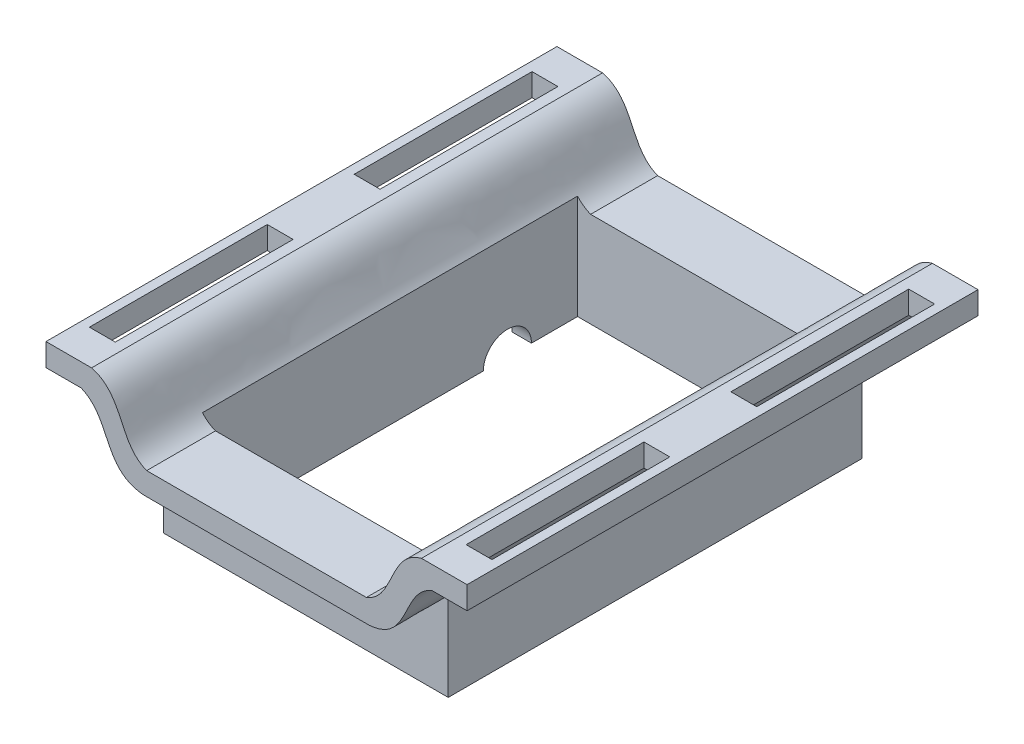
SolidWorks part; units mm, degrees
ref_plane "Front Plane" through (0, 0, 0) normal (0, 0, 1) x (1, 0, 0)
ref_plane "Top Plane" through (0, 0, 0) normal (0, 1, 0) x (1, 0, 0)
ref_plane "Right Plane" through (0, 0, 0) normal (1, 0, 0) x (0, 0, -1)
sketch "Sketch1" plane through (0, 0, 0) normal (0, 0, 1) x (1, 0, 0)
  line L0 (-25.5, 0) -> (25.5, 0) construction
  line L1 (-16.9862, -15) -> (16.9862, -15)
  line L2 (-17.4523, -18.5) -> (17.4523, -18.5)
  line L3 (-25.5, -15) -> (25.5, -15) construction
  line L4 (-25.5, -5.5) -> (-32.5504, -5.5)
  line L5 (-32.5504, -5.5) -> (-32.5504, -9)
  line L6 (-32.5504, -9) -> (-27.1222, -9)
  line L7 (-25.5, -18.5) -> (25.5, -18.5) construction
  line L8 (0, 0) -> (0, -48.7682)
  line L9 (32.5504, -9) -> (27.1222, -9)
  line L10 (32.5504, -5.5) -> (32.5504, -9)
  line L11 (25.5, -5.5) -> (32.5504, -5.5)
  spline S0 degree 3 poles (-25.5, -5.5) (-23.2312, -6.0921) (-20.8572, -9.7633) (-19.4057, -14.0325) (-16.9862, -15) knots 0 0 0 0 0.466176 1 1 1 1
  spline S1 degree 3 poles (-27.1222, -9) (-22.3806, -10.9548) (-23.8233, -17.9686) (-17.4523, -18.5) knots 0 0 0 0 1 1 1 1
  spline S2 degree 3 poles (27.1222, -9) (22.3806, -10.9548) (23.8233, -17.9686) (17.4523, -18.5) knots 0 0 0 0 1 1 1 1
  spline S3 degree 3 poles (25.5, -5.5) (23.2312, -6.0921) (20.8572, -9.7633) (19.4057, -14.0325) (16.9862, -15) knots 0 0 0 0 0.466176 1 1 1 1
  point P4 (0, 0)
  point P32 (0, 0)
  point P33 (0, 0)
  dimension "D1" = 15
  dimension "D2" = 3.5
extrude "Boss-Extrude1" add sketch "Sketch1" along normal blind 79 contours L6 S1 L2 L8 L1 S0 L4 L5 | L11 S3 L1 L8 L2 S2 L9 L10 region at (-8.4931, -15.3505, 0) region at (8.4931, -15.3505, 0)
sketch "Sketch2" plane through (0, -18.5, 0) normal (0, -1, 0) x (1, 0, 0)
  line L1 (-17.4523, 0) -> (-17.4523, 79) construction
  line L2 (19, 68.3605) -> (-19, 10.3605) construction
  line L3 (-19, 68.3605) -> (19, 10.3605) construction
  line L4 (-19, 68.3605) -> (19, 68.3605)
  line L5 (-19, 68.3605) -> (-19, 10.3605)
  line L6 (-19, 10.3605) -> (19, 10.3605)
  line L7 (19, 68.3605) -> (19, 10.3605)
  line L8 (22, 71.3605) -> (22, 7.3605)
  line L9 (-22, 7.3605) -> (22, 7.3605)
  line L10 (-22, 71.3605) -> (-22, 7.3605)
  line L11 (-22, 71.3605) -> (22, 71.3605)
  point P4 (0, 53.3635)
  line M6 (17.4523, 0) -> (17.4523, 79)
  line M8 (-17.4523, 79) -> (-17.4523, 0)
  dimension "D1" = 58
  dimension "D2" = 38
  dimension "D3" = 3
extrude "Cut-Extrude1" cut sketch "Sketch2" against normal blind 79 contours L5 L6 L7 L4
extrude "Boss-Extrude2" add sketch "Sketch2<4>" along normal blind 11.2
sketch "Sketch2<4>" plane through (0, -18.5, 0) normal (0, -1, 0) x (1, 0, 0) same geometry as "Sketch2"
extrude "Boss-Extrude3" add sketch "Sketch2<8>" against normal up to surface contours L11 L10 L9 L6 L5 L4 M8 region at (-20.3951, -18.5, 39.3605) up to face at (-20.508, -15.6205, 39.4163)
sketch "Sketch2<8>" plane through (0, -18.5, 0) normal (0, -1, 0) x (1, 0, 0) same geometry as "Sketch2"
extrude "Boss-Extrude4" add sketch "Sketch2<9>" against normal up to surface (2.6318 mm away) contours L11 L4 L7 L6 L9 L8 M6 region at (20.3951, -18.5, 39.3605) up to face at (20.508, -15.6205, 39.4163)
sketch "Sketch2<9>" plane through (0, -18.5, 0) normal (0, -1, 0) x (1, 0, 0) same geometry as "Sketch2"
sketch "Sketch3" plane through (0, -9, 0) normal (0, -1, 0) x (1, 0, 0)
  line L0 (32.5504, 39.5) -> (52.9515, 39.5) construction
  line L1 (32.5504, 79) -> (32.5504, 0) construction
  line L2 (27.1222, 32.7805) -> (31.1222, 5.2805) construction
  line L3 (27.1222, 73.7195) -> (31.1222, 73.7195)
  line L4 (27.1222, 73.7195) -> (27.1222, 46.2195)
  line L5 (27.1222, 46.2195) -> (31.1222, 46.2195)
  line L6 (31.1222, 73.7195) -> (31.1222, 46.2195)
  line L7 (27.1222, 73.7195) -> (31.1222, 46.2195) construction
  line L8 (27.1222, 46.2195) -> (31.1222, 73.7195) construction
  line L9 (27.1222, 5.2805) -> (31.1222, 32.7805) construction
  line L10 (31.1222, 5.2805) -> (31.1222, 32.7805)
  line L11 (27.1222, 32.7805) -> (31.1222, 32.7805)
  line L12 (27.1222, 5.2805) -> (27.1222, 32.7805)
  line L13 (27.1222, 5.2805) -> (31.1222, 5.2805)
  point P4 (29.1222, 59.9695)
  point P13 (29.1222, 19.0305)
  dimension "D1" = 4
  dimension "D2" = 27.5
extrude "Cut-Extrude2" cut sketch "Sketch3" against normal blind 11.2 contours L3 L6 L5 L4 | L11 L10 L13 L12
mirror "Mirror1" about plane through (0, 0, 0) normal (1, 0, 0) of "Cut-Extrude2"
sketch "Sketch4" plane through (-22, 0, 0) normal (-1, 0, 0) x (0, 0, 1)
  line L0 (71.3605, -29.7) -> (7.3605, -29.7) construction
  circle A0 centre (21.2113, -29.7) radius 3.7197
extrude "Cut-Extrude3" cut sketch "Sketch4" against normal blind 11.2
